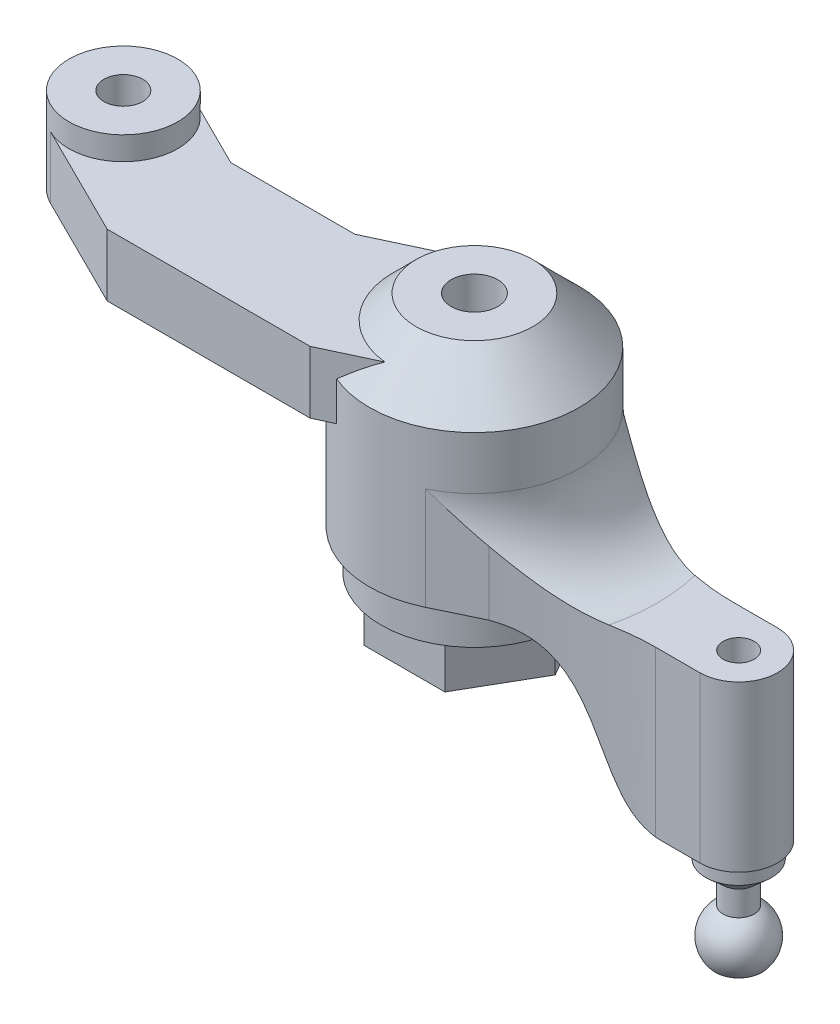
SolidWorks part; units mm, degrees
ref_plane "Front Plane" through (0, 0, 0) normal (0, 0, 1) x (1, 0, 0)
ref_plane "Top Plane" through (0, 0, 0) normal (0, 1, 0) x (1, 0, 0)
ref_plane "Right Plane" through (0, 0, 0) normal (1, 0, 0) x (0, 0, -1)
sketch "Sketch1" plane through (0, 0, 0) normal (0, 1, 0) x (1, 0, 0)
  circle A0 centre (0, 0) radius 6.75
  dimension "D1" = 13.5
extrude "Boss-Extrude1" add sketch "Sketch1" along normal blind 10
sketch "Sketch2" plane through (0, 10, 0) normal (0, 1, 0) x (1, 0, 0)
  circle A0 centre (0, 0) radius 6.75
extrude "Boss-Extrude2" add sketch "Sketch2" along normal blind 3 draft 45
ref_plane "Plane1" through (0, 11.5, 0) normal (0, 1, 0) x (1, 0, 0)
sketch "Sketch7" plane through (0, 11.5, 0) normal (0, 1, 0) x (1, 0, 0)
  line L0 (-19.0875, 0) -> (-19.0875, 7.5571) construction
  line L1 (-1.5875, 0) -> (-1.5875, 8.629) construction
  line L2 (-21.0283, 3.1335) -> (-16.6103, 0.9352)
  line L3 (-16.6103, 0.9352) -> (-8.6273, 0.9352)
  line L4 (-8.6273, 0.9352) -> (-1.9053, 4.0767)
  line L5 (-1.9053, 4.0767) -> (1.9053, -4.0767)
  line L6 (1.9053, -4.0767) -> (-3.8147, -6.75)
  line L7 (-3.8147, -6.75) -> (-16.8787, -6.75)
  line L8 (-24.1467, -3.1335) -> (-16.8787, -6.75)
  line L9 (0, 0) -> (1.1779, 0.5505) construction
  line L10 (-22.5875, 0) -> (0, 0) construction
  circle A0 centre (-22.5875, 0) radius 3.5
  circle A2 centre (0, 0) radius 6.75 construction
  circle A3 centre (0, 0) radius 1.5875
  circle A4 centre (-22.5875, 0) radius 1.25
  point P21 (-0.9547, -5.4134)
  dimension "D1" = 7
  dimension "D4" = 2.5
  dimension "D5" = 3.175
  dimension "D2" = 17.5
  dimension "D3" = 9
extrude "Boss-Extrude5" add sketch "Sketch7" against normal blind 4 contours A3 L5 L4 L3 L2 A0 L8 L7 L6 | A0
sketch "Sketch8" plane through (0, 11.5, 0) normal (0, 1, 0) x (1, 0, 0)
  circle A0 centre (-22.5875, 0) radius 1.25
  circle A1 centre (-22.5875, 0) radius 3.5
extrude "Boss-Extrude6" add sketch "Sketch8" along normal up to surface (1.5 mm away) up to face at (0, 13, 3.75)
sketch "Sketch9" plane through (0, 0, 0) normal (0, -1, 0) x (1, 0, 0)
  line L0 (17, 2.5) -> (14.1589, 2.5)
  line L1 (2.9271, 6.0823) -> (5.6862, 4.7545)
  line L2 (0, 0) -> (2.9271, 0) construction
  line L3 (17, -2.5) -> (14.1589, -2.5)
  line L4 (2.9271, -6.0823) -> (5.6862, -4.7545)
  circle A0 centre (17, 0) radius 2.5
  circle A1 centre (0, 0) radius 6.75 construction
  circle A2 centre (0, 0) radius 6.75
  circle A3 centre (17, 0) radius 1
  spline S0 degree 3 poles (5.6862, 4.7545) (8.3196, 3.4872) (11.1347, 2.5) (14.1589, 2.5) knots 0 0 0 0 1 1 1 1
  spline S1 degree 3 poles (5.6862, -4.7545) (8.3196, -3.4872) (11.1347, -2.5) (14.1589, -2.5) knots 0 0 0 0 1 1 1 1
  circle M5 centre (0, 0) radius 6.75
  dimension "D2" = 5
  dimension "D3" = 2
  dimension "D1" = 17
extrude "Boss-Extrude7" add sketch "Sketch9" against normal blind 1.6 contours L4 S1 L3 A0 L0 S0 L1 M5 | A0
sketch "Sketch10" plane through (0, 0, 0) normal (0, -1, 0) x (1, 0, 0)
  line L14 (14.1589, 2.5) -> (17, 2.5)
  line L15 (14.1589, 2.5) -> (17, 2.5)
  line L16 (14.1589, 1.5) -> (15, 1.5)
  line L17 (17, -2.5) -> (14.1589, -2.5)
  line L18 (17, -2.5) -> (14.1589, -2.5)
  line L19 (17, -1.5) -> (14.1589, -1.5)
  line L20 (5.2526, -3.8534) -> (5.6862, -4.7545)
  line L21 (5.6862, 4.7545) -> (5.2526, 3.8534)
  circle A0 centre (17, 0) radius 1
  circle A1 centre (17, 0) radius 2.5
  spline S11 degree 3 poles (-102.8773, -2992.6357) (36.0466, 3085.9946) (-121.2726, -3063.8089) (378.198, 2977.6866) knots -16.703628 -16.703628 -16.703628 -16.703628 15.861793 15.861793 15.861793 15.861793 only from (5.6862, 4.7545) to (14.1589, 2.5)
  spline S12 degree 3 poles (5.6862, 4.7545) (8.3196, 3.4872) (11.1347, 2.5) (14.1589, 2.5) knots 0 0 0 0 1 1 1 1
  spline S14 degree 3 poles (378.1942, -2977.6413) (-121.2699, 3063.7544) (36.045, -3085.931) (-102.8756, 2992.564) knots -14.861712 -14.861712 -14.861712 -14.861712 17.7035 17.7035 17.7035 17.7035 only from (14.1589, -2.5) to (5.6862, -4.7545)
  spline S15 degree 3 poles (14.1589, -2.5) (11.1347, -2.5) (8.3196, -3.4872) (5.6862, -4.7545) knots 0 0 0 0 1 1 1 1
  spline S16 degree 3 poles (5.2526, 3.8534) (5.9335, 3.5258) (7.3068, 2.9116) (9.485, 2.1503) (11.7531, 1.6325) (13.3627, 1.5) (14.1589, 1.5) knots 0 0 0 0 0.25 0.5 0.75 1 1 1 1
  spline S17 degree 1 poles (14.1589, -1.5) (5.2526, -3.8534) knots 0 0 1 1 construction
  spline S18 degree 3 poles (14.1589, -1.5) (13.3627, -1.5) (11.7531, -1.6325) (9.485, -2.1503) (7.3068, -2.9116) (5.9335, -3.5258) (5.2526, -3.8534) knots 0 0 0 0 0.25 0.5 0.75 1 1 1 1
  dimension "D1" = 0
  dimension "D2" = 0
  dimension "D4" = 1
extrude "Boss-Extrude8" add sketch "Sketch10" along normal blind 9
sketch "Sketch11" plane through (0, 0, 0) normal (0, 0, 1) x (1, 0, 0)
  line L0 (14.5, -9) -> (15, -9)
  line L1 (4.3066, 0) -> (5.3133, 0)
  line L3 (2.9271, 0) -> (5.6862, 0) construction
  line L4 (14.5, -9) -> (4.3718, -9)
  line L5 (4.3718, -9) -> (4.3066, 0)
  spline S0 degree 3 poles (5.3133, 0) (11.5884, 0) (10.2131, -9) (14.5, -9) knots 0 0 0 0 1 1 1 1
extrude "Cut-Extrude2" cut sketch "Sketch11" against normal through all and the other way through all contours S0 L1 L5 L4
sketch "Sketch12" plane through (0, 0, 0) normal (0, -1, 0) x (1, 0, 0)
  circle A0 centre (0, 0) radius 6
  dimension "D1" = 12
extrude "Boss-Extrude9" add sketch "Sketch12" along normal blind 2.5
sketch "Sketch13" plane through (0, -2.5, 0) normal (0, -1, 0) x (1, 0, 0)
  line L1 (-5.1962, 0) -> (-2.5981, -4.5)
  line L2 (-2.5981, -4.5) -> (2.5981, -4.5)
  line L3 (2.5981, -4.5) -> (5.1962, 0)
  line L4 (5.1962, 0) -> (2.5981, 4.5)
  line L5 (2.5981, 4.5) -> (-2.5981, 4.5)
  line L6 (-2.5981, 4.5) -> (-5.1962, 0)
  circle A0 centre (0, 0) radius 4.5 construction
  dimension "D1" = 9
extrude "Boss-Extrude10" add sketch "Sketch13" along normal blind 3.175
sketch "Sketch14" plane through (0, 13, 0) normal (0, 1, 0) x (1, 0, 0)
  circle A0 centre (0, 0) radius 1.5
  dimension "D1" = 3
extrude "Cut-Extrude3" cut sketch "Sketch14" against normal through all
ref_axis "Axis1" through (17, 1.6, 0) along (0, -1, 0)
sketch "Sketch15" plane through (0, 0, 0) normal (0, 0, 1) x (1, 0, 0)
  line L0 (17, -9) -> (17, -15.6)
  line L1 (17, 1.6) -> (17, -9) construction
  line L2 (19.125, -9) -> (19.125, -10)
  line L3 (17, -9) -> (19.5, -9) construction
  line L4 (19.125, -10) -> (18, -11)
  line L5 (18, -11) -> (18, -12.6)
  line L6 (17, -15.6) -> (18.5, -15.6)
  line L7 (19, -14.2988) -> (19, -16.3563) construction
  line L8 (17, -9) -> (19.125, -9)
  arc A0 (18, -12.6) -> (18.5, -15.6) centre (17.057, -14.2988) cw
  dimension "D1" = 1
  dimension "D2" = 1
  dimension "D3" = 1.6
  dimension "D4" = 3
  dimension "D5" = 1
  dimension "D6" = 2.125
  dimension "D7" = 1.5
  dimension "D8" = 4
revolve "Revolve1" add sketch "Sketch15" angle 360 about axis through (17, 1.6, 0) along (0, -1, 0)
fillet "Fillet1" radius 5 1 edges at (6.75, 1.6, 0)
ref_point "Point1"
